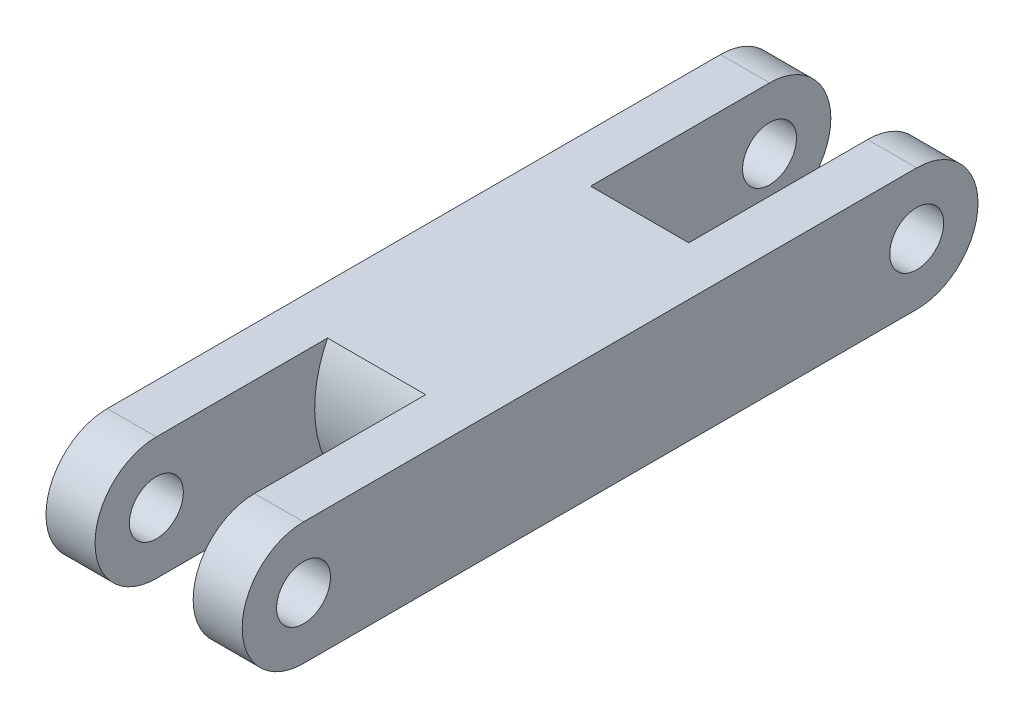
SolidWorks part; units mm, degrees
material "环氧树脂,未充填"
ref_plane "前视基准面" through (0, 0, 0) normal (0, 0, 1) x (1, 0, 0)
ref_plane "上视基准面" through (0, 0, 0) normal (0, 1, 0) x (1, 0, 0)
ref_plane "右视基准面" through (0, 0, 0) normal (1, 0, 0) x (0, 0, -1)
other "Configuration Table"
sketch "草图1" plane through (0, 0, 0) normal (1, 0, 0) x (0, 0, -1)
  line L0 (-12.5, 0) -> (12.5, 0) construction
  line L1 (-12.5, 0) -> (12.5, 0) construction
  line L2 (-12.5, 2.5) -> (12.5, 2.5)
  line L3 (-12.5, -2.5) -> (12.5, -2.5)
  circle A0 centre (12.5, 0) radius 1.1
  arc A1 (-12.5, 2.5) -> (-12.5, -2.5) centre (-12.5, 0) ccw
  arc A2 (12.5, -2.5) -> (12.5, 2.5) centre (12.5, 0) ccw
  circle A3 centre (-12.5, 0) radius 1.1
  point P4 (0, 0)
  point P7 (0, 0)
  dimension "D1" = 2.2
  dimension "D2" = 2.5
  dimension "D3" = 25
extrude "凸台-拉伸1" add sketch "草图1" along normal mid plane 8
sketch "草图2" plane through (0, 0, 0) normal (1, 0, 0) x (0, 0, -1)
  line L0 (-8.5, 0) -> (-5.5206, 2.5)
  line L1 (-5.5206, 2.5) -> (-9.3775, 2.5)
  line L2 (12.5, 2.5) -> (-12.5, 2.5) construction
  line L3 (0, 0) -> (0, 50000) construction
  line L4 (0, 0) -> (-50000, 0) construction
  line L5 (5.5206, 2.5) -> (9.3775, 2.5)
  line L6 (8.5, 0) -> (5.5206, 2.5)
  line L7 (5.5206, -2.5) -> (9.3775, -2.5)
  line L8 (8.5, 0) -> (5.5206, -2.5)
  line L9 (-5.5206, -2.5) -> (-9.3775, -2.5)
  line L10 (-8.5, 0) -> (-5.5206, -2.5)
  circle A0 centre (12.5, 0) radius 4
  circle A1 centre (-12.5, 0) radius 4
  dimension "D1" = 8
  dimension "D2" = 40
extrude "切除-拉伸1" cut sketch "草图2" against normal mid plane 4 contours A1 L0 L1 | A1 L9 L10 | A1 | A0 | A0 L5 L6 | A0 L8 L7
fillet "圆角1" radius 5 2 edges at (0, 0, -8.5) (0, 0, 8.5)
